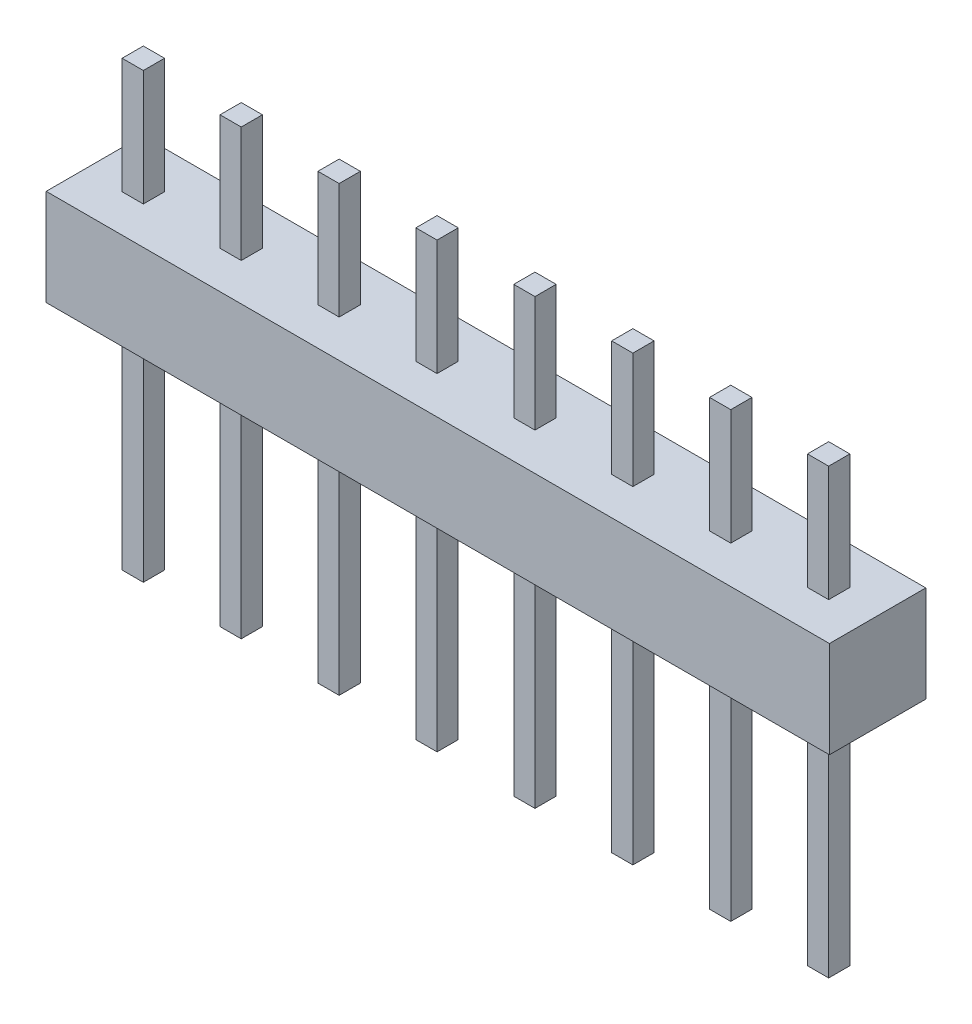
SolidWorks part; units mm, degrees
ref_plane "Front Plane" through (0, 0, 0) normal (0, 0, 1) x (1, 0, 0)
ref_plane "Top Plane" through (0, 0, 0) normal (0, 1, 0) x (1, 0, 0)
ref_plane "Right Plane" through (0, 0, 0) normal (1, 0, 0) x (0, 0, -1)
sketch "Sketch1" plane through (0, 0, 0) normal (0, 0, 1) x (1, 0, 0)
  line L1 (0, 0) -> (20.32, 0)
  line L2 (0, 0) -> (0, 2.5)
  line L3 (0, 2.5) -> (20.32, 2.5)
  line L4 (20.32, 0) -> (20.32, 2.5)
  dimension "D1" = 2.5
  dimension "D2" = 20.32
extrude "Boss-Extrude1" add sketch "Sketch1" along normal mid plane 2.5
sketch "Sketch2" plane through (0, 0, 0) normal (0, -1, 0) x (1, 0, 0)
  line L0 (0, 0) -> (20.32, 0) construction
  line L1 (20.32, 1.25) -> (20.32, -1.25) construction
  line L2 (3.535, -0.275) -> (4.085, -0.275)
  line L3 (0.995, -0.275) -> (1.545, -0.275)
  line L4 (0.995, -0.275) -> (0.995, 0.275)
  line L5 (0.995, 0.275) -> (1.545, 0.275)
  line L6 (1.545, -0.275) -> (1.545, 0.275)
  line L7 (0.995, -0.275) -> (1.545, 0.275) construction
  line L8 (0.995, 0.275) -> (1.545, -0.275) construction
  line L9 (3.535, -0.275) -> (3.535, 0.275)
  line L10 (3.535, 0.275) -> (4.085, 0.275)
  line L11 (4.085, -0.275) -> (4.085, 0.275)
  line L12 (3.535, -0.275) -> (4.085, 0.275) construction
  line L13 (3.535, 0.275) -> (4.085, -0.275) construction
  line L14 (1.27, 0) -> (3.81, 0) construction
  line L15 (6.075, -0.275) -> (6.625, -0.275)
  line L16 (6.075, -0.275) -> (6.075, 0.275)
  line L17 (6.075, 0.275) -> (6.625, 0.275)
  line L18 (6.625, -0.275) -> (6.625, 0.275)
  line L19 (6.075, -0.275) -> (6.625, 0.275) construction
  line L20 (6.075, 0.275) -> (6.625, -0.275) construction
  line L21 (8.615, -0.275) -> (9.165, -0.275)
  line L22 (8.615, -0.275) -> (8.615, 0.275)
  line L23 (8.615, 0.275) -> (9.165, 0.275)
  line L24 (9.165, -0.275) -> (9.165, 0.275)
  line L25 (8.615, -0.275) -> (9.165, 0.275) construction
  line L26 (8.615, 0.275) -> (9.165, -0.275) construction
  line L27 (11.155, -0.275) -> (11.705, -0.275)
  line L28 (11.155, -0.275) -> (11.155, 0.275)
  line L29 (11.155, 0.275) -> (11.705, 0.275)
  line L30 (11.705, -0.275) -> (11.705, 0.275)
  line L31 (11.155, -0.275) -> (11.705, 0.275) construction
  line L32 (11.155, 0.275) -> (11.705, -0.275) construction
  line L33 (13.695, -0.275) -> (14.245, -0.275)
  line L34 (13.695, -0.275) -> (13.695, 0.275)
  line L35 (13.695, 0.275) -> (14.245, 0.275)
  line L36 (14.245, -0.275) -> (14.245, 0.275)
  line L37 (13.695, -0.275) -> (14.245, 0.275) construction
  line L38 (13.695, 0.275) -> (14.245, -0.275) construction
  line L39 (16.235, -0.275) -> (16.785, -0.275)
  line L40 (16.235, -0.275) -> (16.235, 0.275)
  line L41 (16.235, 0.275) -> (16.785, 0.275)
  line L42 (16.785, -0.275) -> (16.785, 0.275)
  line L43 (16.235, -0.275) -> (16.785, 0.275) construction
  line L44 (16.235, 0.275) -> (16.785, -0.275) construction
  line L45 (18.775, -0.275) -> (19.325, -0.275)
  line L46 (18.775, -0.275) -> (18.775, 0.275)
  line L47 (18.775, 0.275) -> (19.325, 0.275)
  line L48 (19.325, -0.275) -> (19.325, 0.275)
  line L49 (18.775, -0.275) -> (19.325, 0.275) construction
  line L50 (18.775, 0.275) -> (19.325, -0.275) construction
  point P5 (1.27, 0)
  point P12 (3.81, 0)
  point P18 (6.35, 0)
  point P23 (8.89, 0)
  point P28 (11.43, 0)
  point P33 (13.97, 0)
  point P38 (16.51, 0)
  point P43 (19.05, 0)
  dimension "D1" = 0.55
  dimension "D3" = 1.27
  dimension "D4" = 2.54
  dimension "D2" = 8
extrude "Boss-Extrude2" add sketch "Sketch2" along normal blind 6 separate body
ref_axis "Axis1" through (1.27, 0, 0) along (0, -1, 0)
ref_axis "Axis2" through (19.05, 0, 0) along (0, -1, 0)
extrude "Boss-Extrude3" add sketch "Sketch2<2>" against normal blind 5.5 separate body
sketch "Sketch2<2>" plane through (0, 0, 0) normal (0, -1, 0) x (1, 0, 0) same geometry as "Sketch2"
